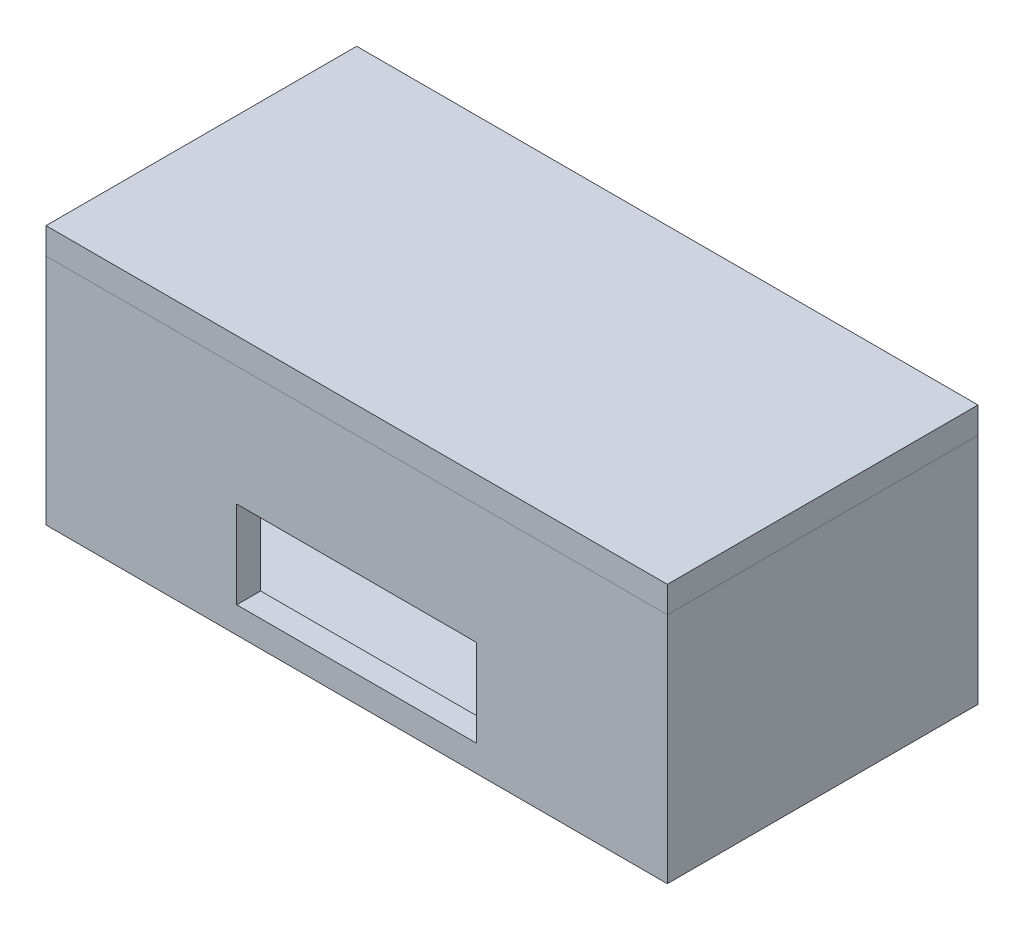
SolidWorks part; units mm, degrees
ref_plane "Alzado" through (0, 0, 0) normal (0, 0, 1) x (1, 0, 0)
ref_plane "Planta" through (0, 0, 0) normal (0, 1, 0) x (1, 0, 0)
ref_plane "Vista lateral" through (0, 0, 0) normal (1, 0, 0) x (0, 0, -1)
sketch "Croquis1" plane through (0, 0, 0) normal (0, 1, 0) x (1, 0, 0)
  line L1 (-65, -32.5) -> (65, -32.5)
  line L2 (-65, -32.5) -> (-65, 32.5)
  line L3 (-65, 32.5) -> (65, 32.5)
  line L4 (65, -32.5) -> (65, 32.5)
  line L5 (-65, -32.5) -> (65, 32.5) construction
  line L6 (-65, 32.5) -> (65, -32.5) construction
  point P0 (0, 0)
  dimension "D1" = 130
  dimension "D2" = 65
extrude "Saliente-Extruir1" add sketch "Croquis1" along normal blind 48.75
shell "Vaciado1" thickness 5 removed face at (0, 48.75, 0)
sketch "Croquis2" plane through (0, 48.75, 0) normal (0, 1, 0) x (1, 0, 0)
  line L0 (-65, -32.5) -> (65, -32.5) construction
  line L1 (-65, 32.5) -> (-65, -32.5) construction
  line L2 (65, 32.5) -> (-65, 32.5) construction
  line L3 (65, -32.5) -> (65, 32.5) construction
  line L8 (-65, -32.5) -> (65, -32.5)
  line L9 (-65, 32.5) -> (-65, -32.5)
  line L10 (65, 32.5) -> (-65, 32.5)
  line L11 (65, -32.5) -> (65, 32.5)
  line L12 (-59.5, -27) -> (59.5, -27)
  line L13 (59.5, -27) -> (59.5, 27)
  line L14 (-59.5, 27) -> (-59.5, -27)
  line L15 (59.5, 27) -> (-59.5, 27)
  line L16 (-60, 27.5) -> (-60, -27.5) construction
  line L17 (0, 27) -> (0, -27) construction
  line L18 (0, 32.5) -> (0, -32.5) construction
  line L19 (-65, 0) -> (65, 0) construction
  line L20 (-59.5, 0) -> (59.5, 0) construction
  line L21 (-60, -27.5) -> (60, -27.5) construction
  line M1 (65, -32.5) -> (65, 32.5)
  line M2 (65, 32.5) -> (-65, 32.5)
  line M3 (-65, 32.5) -> (-65, -32.5)
  line M4 (-65, -32.5) -> (65, -32.5)
  line M5 (60, 27.5) -> (60, -27.5)
  line M6 (60, -27.5) -> (-60, -27.5)
  line M7 (-60, -27.5) -> (-60, 27.5)
  line M8 (-60, 27.5) -> (60, 27.5)
  dimension "D1" = 5.5
  dimension "D2" = 0.5
  dimension "D3" = 0.5
extrude "Saliente-Extruir2" add sketch "Croquis2" along normal blind 5.5 separate body contours L15 L13 L12 L14 M5 M8 M7 M6 | M4 M1 M2 M3 M8 M5 M6 M7 | L13 L15 L14 L12 region at (-63.5466, 48.75, 0) region at (0, 48.75, 0) region at (59.868, 48.75, 0)
extrude "Saliente-Extruir3" add sketch "Croquis2<4>" against normal blind 5.5 contours L13 L15 L14 L12 region at (0, 48.75, 0)
sketch "Croquis2<4>" plane through (0, 48.75, 0) normal (0, 1, 0) x (1, 0, 0) same geometry as "Croquis2"
sketch "Croquis3" plane through (0, 0, 32.5) normal (0, 0, 1) x (1, 0, 0)
  line L0 (0, 48.75) -> (0, 0) construction
  line L1 (-65, 48.75) -> (65, 48.75) construction
  line L2 (-65, 24.375) -> (65, 24.375) construction
  line L3 (-65, 48.75) -> (-65, 0) construction
  line L4 (65, 48.75) -> (65, 0) construction
  line L5 (-65, 0) -> (65, 0) construction
  line L6 (-25.1, 5.5) -> (25.1, 5.5)
  line L7 (-25.1, 5.5) -> (-25.1, 23.76)
  line L8 (-25.1, 23.76) -> (25.1, 23.76)
  line L9 (25.1, 5.5) -> (25.1, 23.76)
  line L10 (-25.1, 5.5) -> (25.1, 23.76) construction
  line L11 (-25.1, 23.76) -> (25.1, 5.5) construction
  point P11 (0, 14.63)
  point P16 (0, 20.2935)
  dimension "D1" = 50.2
  dimension "D2" = 18.26
  dimension "D3" = 5.5
extrude "Cortar-Extruir1" cut sketch "Croquis3" against normal up to next (5 mm away)
equation "\"D1\"=32.0338"
equation "\"D\"=32"
equation "\"D2\"=50"
equation "\"D2@Croquis1\"=\"D1@Croquis1\"/2"
equation "\"D1@Saliente-Extruir1\"=(\"D2@Croquis1\"+\"D1@Croquis1\")/4"
equation "\"D1Croquis2\"= \"D1@Croquis2\""
equation "\"D1@Saliente-Extruir2\"=\"D1Croquis2\""
equation "\"D1@Saliente-Extruir3\"=\"D1Croquis2\""
equation "\"D3@Croquis2\"=\"D2@Croquis2\""
equation "\"D3@Croquis3\"=\"D1Croquis2\""
